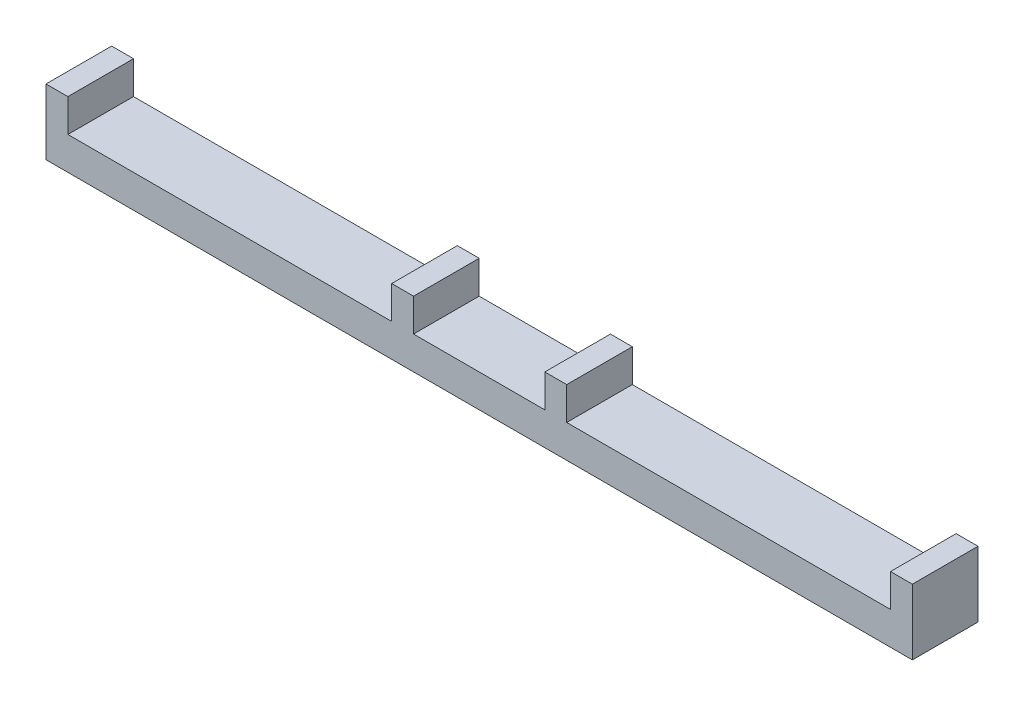
SolidWorks part; units mm, degrees
material "ABS"
ref_plane "前视基准面" through (0, 0, 0) normal (0, 0, 1) x (1, 0, 0)
ref_plane "上视基准面" through (0, 0, 0) normal (0, 1, 0) x (1, 0, 0)
ref_plane "右视基准面" through (0, 0, 0) normal (1, 0, 0) x (0, 0, -1)
sketch "草图1" plane through (0, 0, 0) normal (0, 0, 1) x (1, 0, 0)
  line L0 (-94, 7.5) -> (-99, 7.5)
  line L1 (99, 7.5) -> (94, 7.5)
  line L2 (99, 7.5) -> (99, -7.5)
  line L3 (99, -7.5) -> (-99, -7.5)
  line L4 (-99, 7.5) -> (-99, -7.5)
  line L5 (99, 7.5) -> (-99, -7.5) construction
  line L6 (99, -7.5) -> (-99, 7.5) construction
  line L8 (-94, 7.5) -> (-94, 0)
  line L9 (-94, 0) -> (94, 0)
  line L10 (94, 7.5) -> (94, 0)
  point P0 (0, 0)
  point P10 (0, 0)
  dimension "D1" = 198
  dimension "D2" = 188
  dimension "D3" = 15
extrude "凸台-拉伸1" add sketch "草图1" along normal blind 15
sketch "草图2" plane through (0, 0, 15) normal (0, 0, 1) x (1, 0, 0)
  line L1 (20, -7.5) -> (-20, -7.5)
  line L2 (20, -7.5) -> (20, 7.5)
  line L3 (20, 7.5) -> (15, 7.5)
  line L4 (-20, -7.5) -> (-20, 7.5)
  line L5 (20, -7.5) -> (-20, 7.5) construction
  line L6 (20, 7.5) -> (-20, -7.5) construction
  line L7 (99, 7.5) -> (94, 7.5) construction
  line L8 (94, 0) -> (-94, 0) construction
  line L10 (-15, 7.5) -> (-15, 0)
  line L11 (-15, 0) -> (15, 0)
  line L12 (15, 7.5) -> (15, 0)
  line L13 (-15, 7.5) -> (-20, 7.5)
  point P0 (0, 0)
  point P14 (0, 0)
  dimension "D1" = 40
  dimension "D2" = 5
extrude "凸台-拉伸2" add sketch "草图2" against normal up to surface (15 mm away) up to face at (0, 1.875, 0)
